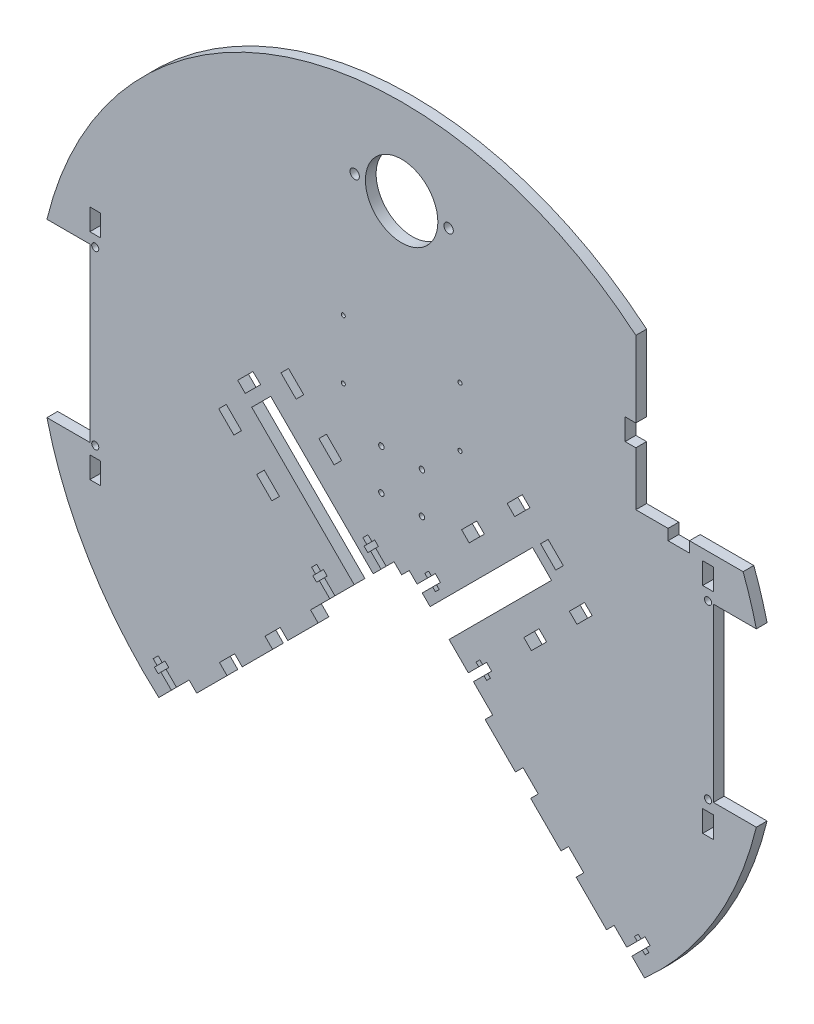
SolidWorks part; units mm, degrees
ref_plane "Front Plane" through (0, 0, 0) normal (0, 0, 1) x (1, 0, 0)
ref_plane "Top Plane" through (0, 0, 0) normal (0, 1, 0) x (1, 0, 0)
ref_plane "Right Plane" through (0, 0, 0) normal (1, 0, 0) x (0, 0, -1)
sketch "Sketch1" plane through (0, 0, 0) normal (0, 0, 1) x (1, 0, 0)
  circle A0 centre (0, 0) radius 215.9
  dimension "D1" = 431.8
extrude "Base Plate Extrusion" add sketch "Sketch1" along normal blind 6.35
sketch "Sketch2" plane through (0, 0, 6.35) normal (0, 0, 1) x (1, 0, 0)
  line L0 (0, 0) -> (0, -230.9791) construction
  line L1 (0, -17.4608) -> (143.6841, -161.1449)
  line L2 (0, -17.4608) -> (-143.6841, -161.1449)
  circle A1 centre (0, 0) radius 215.9 construction
  arc A2 (143.6841, -161.1449) -> (-143.6841, -161.1449) centre (0, 0) cw
  dimension "D1" = 90
  dimension "D2" = 203.2
extrude "V Funnel Cut" cut sketch "Sketch2" against normal through all
sketch "Sketch3" plane through (0, 0, 6.35) normal (0, 0, 1) x (1, 0, 0)
  line L0 (0, 0) -> (251.7982, 0) construction
  line L1 (209.8384, 50.8) -> (184.4384, 50.8)
  line L2 (209.8384, 50.8) -> (209.8384, -50.8)
  line L3 (209.8384, -50.8) -> (184.4384, -50.8)
  line L4 (184.4384, 50.8) -> (184.4384, -50.8)
  arc A0 (143.6841, -161.1449) -> (-143.6841, -161.1449) centre (0, 0) ccw construction
  arc A1 (209.8384, 50.8) -> (209.8384, -50.8) centre (0, 0) cw
  arc M7 (143.6841, -161.1449) -> (-143.6841, -161.1449) centre (0, 0) ccw
  dimension "D1" = 25.4
  dimension "D2" = 101.6
extrude "Wheel Track Cut" cut sketch "Sketch3" against normal through all contours L2 L0 A1 | L4 L0 L2 L1 | L0 L4 L3 L2 | L0 L2 M7 region at (197.1384, 25.4, 6.35) region at (197.1384, -25.4, 6.35) region at (212.266, 19.0862, 6.35) region at (212.266, -19.0862, 6.35)
mirror "Wheel Track Cut Mirror" about plane through (0, 0, 0) normal (1, 0, 0) of "Wheel Track Cut"
sketch "Sketch4" plane through (0, 0, 6.35) normal (0, 0, 1) x (1, 0, 0)
  line L0 (88.68, 15.0926) -> (77.4547, 26.3179)
  line L1 (88.68, 15.0926) -> (28.0633, -45.5241)
  line L2 (77.4547, 26.3179) -> (16.838, -34.2988)
  line L3 (28.0633, -45.5241) -> (16.838, -34.2988)
  line L4 (84.3174, 21.9553) -> (56.956, -5.4061) construction
  line L5 (65.1069, -1.7454) -> (69.5826, 2.7303) construction
  line L6 (65.0924, 7.2204) -> (60.6167, 2.7447) construction
  line L7 (143.6841, -161.1449) -> (0, -17.4608) construction
  dimension "D1" = 15.875
  dimension "D2" = 85.725
extrude "Cut-Extrude3" cut sketch "Sketch4" against normal through all
sketch "Sketch5" plane through (0, 0, 6.35) normal (0, 0, 1) x (1, 0, 0)
  line L0 (-4.4901, -21.951) -> (0, -17.4608)
  line L1 (-4.4901, -21.951) -> (0, -26.4411)
  line L2 (0, -17.4608) -> (4.4901, -21.951)
  line L3 (0, -26.4411) -> (4.4901, -21.951)
  line L4 (0, -17.4608) -> (-143.6841, -161.1449) construction
  line L6 (4.4901, -21.951) -> (0, -26.4411) construction
  dimension "D1" = 6.35
extrude "Boss-Extrude2" add sketch "Sketch5" against normal up to surface (6.35 mm away) up to face at (14.0691, -14.8765, 0)
mirror "Mirror2" about plane through (0, 0, 0) normal (1, 0, 0) of "Cut-Extrude3"
sketch "Sketch6" plane through (8.7304, -8.7304, 0) normal (0.7071, -0.7071, 0) x (0, 0, -1)
  line L0 (-6.35, -52.0342) -> (-6.35, -215.5467) construction
  line L1 (-6.35, -190.1467) -> (0, -190.1467)
  line L2 (-6.35, -190.1467) -> (-6.35, -164.7467)
  line L3 (-6.35, -164.7467) -> (0, -164.7467)
  line L4 (0, -190.1467) -> (0, -164.7467)
  line L5 (0, -52.0342) -> (0, -215.5467) construction
  dimension "D1" = 25.4
  dimension "D2" = 25.4
extrude "Boss-Extrude3" add sketch "Sketch6" along normal blind 6.35
pattern_linear "LPattern1" count 3 spacing 38.1 along (0.7071, 0.7071, 0) of "Boss-Extrude3"
sketch "Sketch7" plane through (-8.7304, -8.7304, 0) normal (-0.7071, -0.7071, 0) x (0, 0, 1)
  line L0 (6.35, -215.5467) -> (6.35, -52.0342) construction
  line L1 (6.35, -164.7467) -> (0, -164.7467)
  line L2 (6.35, -164.7467) -> (6.35, -190.1467)
  line L3 (6.35, -190.1467) -> (0, -190.1467)
  line L4 (0, -164.7467) -> (0, -190.1467)
  line L5 (0, -215.5467) -> (0, -52.0342) construction
  dimension "D1" = 25.4
  dimension "D2" = 25.4
extrude "Boss-Extrude4" add sketch "Sketch7" along normal blind 6.35
pattern_linear "LPattern2" count 3 spacing 38.1 along (-0.7071, 0.7071, 0) of "Boss-Extrude4"
sketch "Sketch8" plane through (0, 0, 0) normal (0, 0, -1) x (-1, 0, 0)
  line L0 (-72.2911, -22.4) -> (-81.2713, -13.4197)
  line L1 (-81.2713, -13.4197) -> (-85.7614, -17.9098)
  line L2 (-85.7614, -17.9098) -> (-76.7812, -26.8901)
  line L3 (-76.7812, -26.8901) -> (-72.2911, -22.4)
  line L4 (-99.2318, 4.5408) -> (-103.722, 0.0507)
  line L5 (-103.722, 0.0507) -> (-112.7022, 9.0309)
  line L6 (-112.7022, 9.0309) -> (-108.2121, 13.521)
  line L7 (-108.2121, 13.521) -> (-99.2318, 4.5408)
  line L8 (-95.6515, 26.0817) -> (-86.6712, 35.0619)
  line L9 (-86.6712, 35.0619) -> (-82.1811, 30.5718)
  line L10 (-82.1811, 30.5718) -> (-91.1613, 21.5915)
  line L11 (-91.1613, 21.5915) -> (-95.6515, 26.0817)
  line L12 (-66.9029, 36.8697) -> (-62.4128, 41.3598)
  line L13 (-62.4128, 41.3598) -> (-71.393, 50.3401)
  line L14 (-71.393, 50.3401) -> (-75.8832, 45.85)
  line L15 (-75.8832, 45.85) -> (-66.9029, 36.8697)
  line L16 (-48.9424, 18.9092) -> (-44.4523, 23.3993)
  line L17 (-44.4523, 23.3993) -> (-35.472, 14.4191)
  line L18 (-35.472, 14.4191) -> (-39.9621, 9.9289)
  line L19 (-39.9621, 9.9289) -> (-48.9424, 18.9092)
extrude "Cut-Extrude4" cut sketch "Sketch8" against normal blind 6.35
sketch "Sketch9" plane through (0, 0, 0) normal (0, 0, -1) x (-1, 0, 0)
  line L0 (-138.5621, 165.5698) -> (-138.5621, 76.2)
  line L1 (-138.5621, 76.2) -> (-202.0059, 76.2)
  line L2 (-132.2121, 76.2) -> (-157.6121, 76.2) construction
  line L3 (-138.5621, 152.4) -> (-138.5621, 120.65) construction
  arc A0 (209.8384, 50.8) -> (-209.8384, 50.8) centre (0, 0) ccw construction
  arc A1 (-202.0059, 76.2) -> (-138.5621, 165.5698) centre (0, 0) cw
extrude "Cut-Extrude5" cut sketch "Sketch9" against normal through all
sketch "Sketch10" plane through (0, 0, 0) normal (0, 0, -1) x (-1, 0, 0)
  line L0 (48.9424, 18.9092) -> (39.9621, 9.9289)
  line L1 (39.9621, 9.9289) -> (35.472, 14.4191)
  line L2 (35.472, 14.4191) -> (44.4523, 23.3993)
  line L3 (44.4523, 23.3993) -> (48.9424, 18.9092)
  line L4 (62.4128, 32.3796) -> (57.9227, 36.8697)
  line L5 (57.9227, 36.8697) -> (66.9029, 45.85)
  line L6 (66.9029, 45.85) -> (71.393, 41.3598)
  line L7 (71.393, 41.3598) -> (62.4128, 32.3796)
  line L8 (88.0065, 33.7266) -> (83.4195, 29.3333)
  line L9 (83.4195, 29.3333) -> (92.4966, 20.2562)
  line L10 (92.4966, 20.2562) -> (96.9868, 24.7464)
  line L11 (96.9868, 24.7464) -> (88.0065, 33.7266)
  line L12 (103.722, 9.0309) -> (94.7417, 0.0507)
  line L13 (94.7417, 0.0507) -> (99.2318, -4.4395)
  line L14 (99.2318, -4.4395) -> (108.2121, 4.5408)
  line L15 (108.2121, 4.5408) -> (103.722, 9.0309)
  line L16 (85.7614, -17.9098) -> (81.2713, -13.4197)
  line L17 (81.2713, -13.4197) -> (72.2911, -22.4)
  line L18 (72.2911, -22.4) -> (76.7812, -26.8901)
  line L19 (76.7812, -26.8901) -> (85.7614, -17.9098)
extrude "Cut-Extrude6" cut sketch "Sketch10" against normal blind 6.35
sketch "Sketch11" plane through (0, 0, 0) normal (0, 0, -1) x (-1, 0, 0)
  line L1 (184.4384, -69.85) -> (178.0884, -69.85)
  line L2 (184.4384, -69.85) -> (184.4384, -57.15)
  line L3 (184.4384, -57.15) -> (178.0884, -57.15)
  line L4 (178.0884, -69.85) -> (178.0884, -57.15)
  line L5 (184.4384, 57.15) -> (178.0884, 57.15)
  line L6 (184.4384, 57.15) -> (184.4384, 69.85)
  line L7 (184.4384, 69.85) -> (178.0884, 69.85)
  line L8 (178.0884, 57.15) -> (178.0884, 69.85)
  line L9 (-178.0884, -69.85) -> (-184.4384, -69.85)
  line L10 (-178.0884, -69.85) -> (-178.0884, -57.15)
  line L11 (-178.0884, -57.15) -> (-184.4384, -57.15)
  line L12 (-184.4384, -69.85) -> (-184.4384, -57.15)
  line L13 (-178.0884, 57.15) -> (-184.4384, 57.15)
  line L14 (-178.0884, 57.15) -> (-178.0884, 69.85)
  line L15 (-178.0884, 69.85) -> (-184.4384, 69.85)
  line L16 (-184.4384, 57.15) -> (-184.4384, 69.85)
extrude "Cut-Extrude7" cut sketch "Sketch11" against normal blind 6.35
sketch "Sketch12" plane through (0, 0, 0) normal (0, 0, -1) x (-1, 0, 0)
  line L0 (-202.0059, 76.2) -> (-138.5621, 76.2) construction
  line L1 (-157.6121, 69.85) -> (-170.284, 69.85)
  line L2 (-157.6121, 69.85) -> (-157.6121, 76.2)
  line L3 (-157.6121, 76.2) -> (-170.284, 76.2)
  line L4 (-170.284, 69.85) -> (-170.284, 76.2)
  line L5 (-138.5621, 76.2) -> (-138.5621, 165.5698) construction
  line L6 (-132.2121, 120.65) -> (-138.5621, 120.65)
  line L7 (-132.2121, 120.65) -> (-132.2121, 107.95)
  line L8 (-132.2121, 107.95) -> (-138.5621, 107.95)
  line L9 (-138.5621, 120.65) -> (-138.5621, 107.95)
  line L10 (-138.5621, 107.95) -> (-132.2121, 107.95) construction
extrude "Cut-Extrude8" cut sketch "Sketch12" against normal blind 6.35
sketch "Sketch13" plane through (0, 0, 6.35) normal (0, 0, 1) x (1, 0, 0)
  circle A0 centre (0, 165.1) radius 21.4313
  circle A1 centre (27.7813, 165.1) radius 2.7781
  circle A2 centre (-27.7812, 165.1) radius 2.7781
extrude "Cut-Extrude9" cut sketch "Sketch13" against normal through all
sketch "Sketch14" plane through (0, 0, 6.35) normal (0, 0, 1) x (1, 0, 0)
  line L0 (184.4384, 48.6664) -> (178.0884, 52.9336) construction
  line L1 (184.4384, 50.8) -> (184.4384, -50.8) construction
  line L2 (178.0884, 48.6664) -> (184.4384, 48.6664) construction
  line L3 (184.4384, 52.9336) -> (178.0884, 48.6664) construction
  line L4 (184.4384, -52.9336) -> (178.0884, -48.6664) construction
  line L5 (184.4384, -48.6664) -> (178.0884, -52.9336) construction
  line L6 (178.0884, -48.6664) -> (184.4384, -48.6664) construction
  circle A0 centre (181.2634, 50.8) radius 2.0955
  circle A1 centre (181.2634, -50.8) radius 2.0955
  dimension "D1" = 4.191
extrude "Cut-Extrude10" cut sketch "Sketch14" against normal through all
mirror "Mirror3" about plane through (0, 0, 0) normal (1, 0, 0) of "Cut-Extrude10"
sketch "Sketch15" plane through (0, 0, 6.35) normal (0, 0, 1) x (1, 0, 0)
  line L0 (-134.7038, -152.1647) -> (-152.6084, -134.2601) construction
  line L1 (-125.7236, -143.1844) -> (-143.6841, -161.1449) construction
  line L2 (-40.9724, -58.4333) -> (-60.7132, -38.6924) construction
  line L3 (-28.0633, -45.5241) -> (-53.8815, -71.3424) construction
  line L4 (-10.6641, -28.1249) -> (-27.2834, -11.5055) construction
  line L5 (-4.4901, -21.951) -> (-16.838, -34.2988) construction
  line B0 (-136.2125, -153.6734) -> (-133.1952, -150.656)
  line B1 (-141.6366, -142.2146) -> (-140.0022, -140.5801)
  line B2 (-140.0022, -140.5801) -> (-137.7571, -142.8252)
  line B3 (-137.7571, -142.8252) -> (-139.3915, -144.4596)
  line B4 (-139.3915, -144.4596) -> (-133.1952, -150.656)
  line B5 (-141.6366, -142.2146) -> (-143.9715, -139.8797)
  line B6 (-143.9715, -139.8797) -> (-146.9888, -142.8971)
  line B7 (-144.654, -145.2319) -> (-146.9888, -142.8971)
  line B8 (-142.4089, -147.477) -> (-136.2125, -153.6734)
  line B9 (-144.0433, -149.1114) -> (-142.4089, -147.477)
  line B10 (-146.2884, -146.8663) -> (-144.0433, -149.1114)
  line B11 (-144.654, -145.2319) -> (-146.2884, -146.8663)
  line B12 (-42.4811, -59.9419) -> (-39.4637, -56.9246)
  line B13 (-47.9052, -48.4831) -> (-46.2708, -46.8487)
  line B14 (-46.2708, -46.8487) -> (-44.0257, -49.0938)
  line B15 (-44.0257, -49.0938) -> (-45.6601, -50.7282)
  line B16 (-45.6601, -50.7282) -> (-39.4637, -56.9246)
  line B17 (-47.9052, -48.4831) -> (-50.24, -46.1483)
  line B18 (-50.24, -46.1483) -> (-53.2574, -49.1656)
  line B19 (-50.9225, -51.5005) -> (-53.2574, -49.1656)
  line B20 (-48.6775, -53.7456) -> (-42.4811, -59.9419)
  line B21 (-50.3119, -55.38) -> (-48.6775, -53.7456)
  line B22 (-52.5569, -53.1349) -> (-50.3119, -55.38)
  line B23 (-50.9225, -51.5005) -> (-52.5569, -53.1349)
  line B24 (-12.1727, -29.6336) -> (-9.1554, -26.6162)
  line B25 (-17.5968, -18.1748) -> (-15.9624, -16.5404)
  line B26 (-15.9624, -16.5404) -> (-13.7173, -18.7854)
  line B27 (-13.7173, -18.7854) -> (-15.3517, -20.4198)
  line B28 (-15.3517, -20.4198) -> (-9.1554, -26.6162)
  line B29 (-17.5968, -18.1748) -> (-19.9317, -15.8399)
  line B30 (-19.9317, -15.8399) -> (-22.949, -18.8573)
  line B31 (-20.6142, -21.1921) -> (-22.949, -18.8573)
  line B32 (-18.3691, -23.4372) -> (-12.1727, -29.6336)
  line B33 (-20.0035, -25.0716) -> (-18.3691, -23.4372)
  line B34 (-22.2486, -22.8265) -> (-20.0035, -25.0716)
  line B35 (-20.6142, -21.1921) -> (-22.2486, -22.8265)
sketch_block_instance "TSlot-1"
sketch_block "TSlot" parameters "D1"=3.302, "D2"=3.175
sketch_block_instance "TSlot-3"
sketch_block_instance "TSlot-4"
extrude "Cut-Extrude11" cut sketch "Sketch15" against normal through all
mirror "Mirror4" about plane through (0, 0, 0) normal (1, 0, 0) of "Cut-Extrude11"
sketch "Sketch16" plane through (0, 0, 6.35) normal (0, 0, 1) x (1, 0, 0)
  line L0 (0, 0) -> (0, 33.3041) construction
  line L1 (-12, 9.525) -> (12, 9.525) construction
  line L2 (-12, 9.525) -> (-12, 33.525) construction
  line L3 (-12, 33.525) -> (12, 33.525) construction
  line L4 (12, 9.525) -> (12, 33.525) construction
  line L5 (-12, 9.525) -> (12, 33.525) construction
  line L6 (-12, 33.525) -> (12, 9.525) construction
  circle A0 centre (-12, 33.525) radius 1.6
  circle A1 centre (12, 33.525) radius 1.6
  circle A2 centre (12, 9.525) radius 1.6
  circle A3 centre (-12, 9.525) radius 1.6
  point P0 (0, 21.525)
  dimension "D2" = 3.2
  dimension "D1" = 24
  dimension "D3" = 9.525
extrude "Gyro Holes" cut sketch "Sketch16" against normal through all
sketch "Sketch17" plane through (0, 0, 6.35) normal (0, 0, 1) x (1, 0, 0)
  circle A0 centre (-34.5281, 89.2969) radius 1.1906
  circle A1 centre (34.5281, 89.2969) radius 1.1906
  circle A2 centre (34.5281, 54.3719) radius 1.1906
  circle A3 centre (-34.5281, 54.3719) radius 1.1906
  circle A6 centre (-34.5281, 54.3719) radius 1.1906 construction
extrude "Motor Driver Holes" cut sketch "Sketch17" against normal through all
